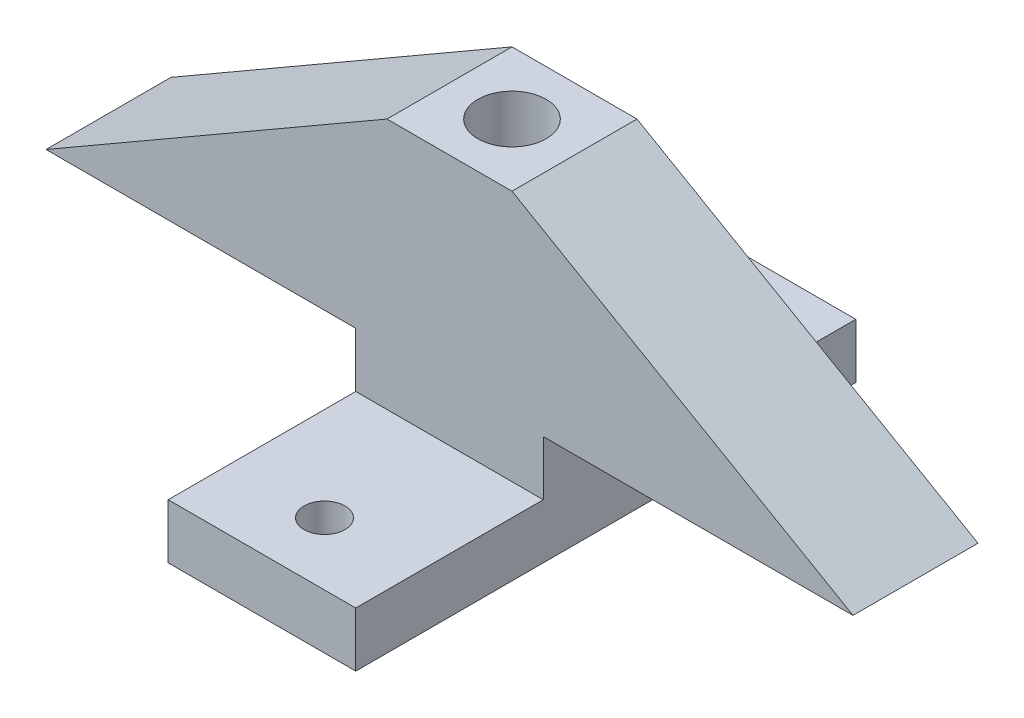
SolidWorks part; units mm, degrees
material "PET"
ref_plane "Front Plane" through (0, 0, 0) normal (0, 0, 1) x (1, 0, 0)
ref_plane "Top Plane" through (0, 0, 0) normal (0, 1, 0) x (1, 0, 0)
ref_plane "Right Plane" through (0, 0, 0) normal (1, 0, 0) x (0, 0, -1)
sketch "Sketch1" plane through (0, 0, 0) normal (0, 0, 1) x (1, 0, 0)
  line L0 (0, 0) -> (0, 22.225)
  line L1 (0, 22.225) -> (-62.932, 22.225)
  line L2 (-62.932, 22.225) -> (6.35, 62.225)
  line L3 (6.35, 62.225) -> (31.75, 62.225)
  line L4 (31.75, 62.225) -> (101.032, 22.225)
  line L5 (101.032, 22.225) -> (38.1, 22.225)
  line L6 (38.1, 22.225) -> (38.1, 0)
  line L7 (38.1, 0) -> (0, 0)
  point P9 (19.05, 62.225)
  point P10 (19.05, 0)
  dimension "D1" = 40
  dimension "D2" = 38.1
  dimension "D3" = 30
  dimension "D4" = 30
  dimension "D5" = 25.4
  dimension "D6" = 22.225
extrude "Boss-Extrude1" add sketch "Sketch1" along normal blind 25.4
sketch "Sketch2" plane through (0, 0, 25.4) normal (0, 0, 1) x (1, 0, 0)
  line L0 (38.1, 0) -> (38.1, 22.225) construction
  line L1 (0, 0) -> (38.1, 0)
  line L2 (0, 0) -> (0, 11.1125)
  line L3 (0, 11.1125) -> (38.1, 11.1125)
  line L4 (38.1, 0) -> (38.1, 11.1125)
extrude "Boss-Extrude2" add sketch "Sketch2" along normal blind 38.1
sketch "Sketch3" plane through (0, 0, 0) normal (0, 0, -1) x (-1, 0, 0)
  line L0 (0, 22.225) -> (0, 0) construction
  line L1 (-38.1, 0) -> (0, 0)
  line L2 (-38.1, 0) -> (-38.1, 11.1125)
  line L3 (-38.1, 11.1125) -> (0, 11.1125)
  line L4 (0, 0) -> (0, 11.1125)
extrude "Boss-Extrude3" add sketch "Sketch3" along normal blind 38.1
hole_wizard "Ø0.328in Dowel Hole1" positions "Sketch4" profile "Sketch5" hole size "Ø1.0" standard "ISO" end condition through all
sketch "Sketch4" plane through (0, 11.1125, 0) normal (0, 1, 0) x (1, 0, 0)
  point P0 (19.05, 25.4)
  point P2 (19.05, -50.8)
  dimension "D1" = 12.7
  dimension "D2" = 19.05
  dimension "D3" = 12.7
  dimension "D4" = 19.05
sketch "Sketch5" plane through (19.05, 11.1125, -25.4) normal (1, 0, 0) x (0, 0, 1)
  line L0 (0, 0) -> (0, 11.1125)
  line L1 (0, 11.1125) -> (4.1656, 11.1125)
  line L2 (4.1656, 11.1125) -> (4.1656, 0)
  line L5 (4.1656, 0) -> (0, 0)
  line L11 (0, -6.35) -> (0, 107.95) construction
  dimension "Thru Hole Dia." = 8.3312
  dimension "Thru Hole Depth" = 11.1125
hole_wizard "Ø0.55in Dowel Hole2" positions "Sketch7" profile "Sketch6" hole size "Ø1.0" standard "ISO"
sketch "Sketch7" plane through (0, 62.225, 0) normal (0, 1, 0) x (1, 0, 0)
  point P0 (19.05, -12.7)
  dimension "D1" = 12.7
  dimension "D2" = 12.7
sketch "Sketch6" plane through (19.05, 62.225, 12.7) normal (1, 0, 0) x (0, 0, 1)
  line L0 (0, 0) -> (0, 39.2261)
  line L1 (0, 39.2261) -> (6.9469, 35.052)
  line L2 (6.9469, 35.052) -> (6.9469, 0)
  line L5 (6.9469, 0) -> (0, 0)
  line L10 (0, 39.2261) -> (-6.9469, 35.052) construction
  line L11 (0, -6.35) -> (0, 107.95) construction
  dimension "Hole Dia." = 13.8938
  dimension "Hole Depth" = 35.052
  dimension "Drill Angle" = 118
